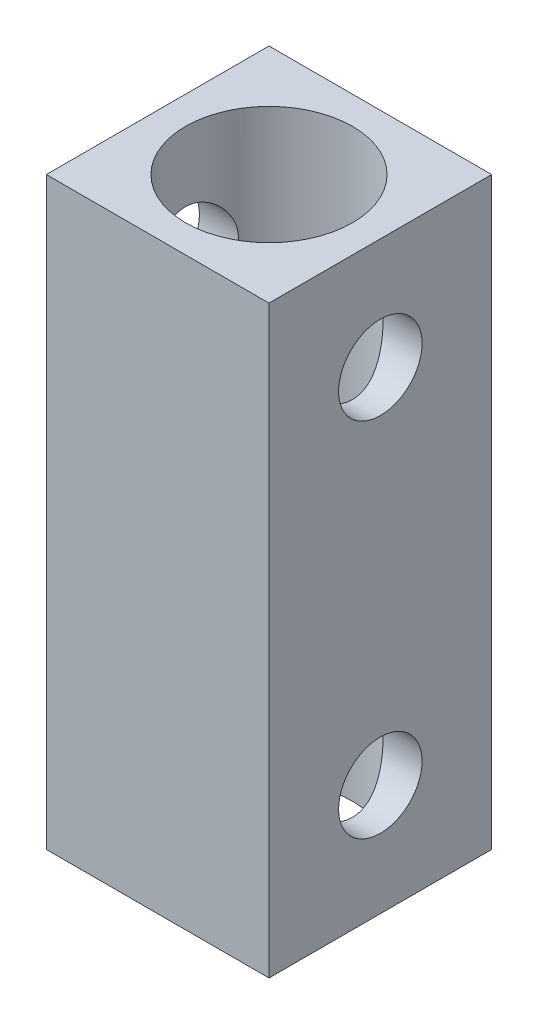
SolidWorks part; units mm, degrees
ref_plane "Front Plane" through (0, 0, 0) normal (0, 0, 1) x (1, 0, 0)
ref_plane "Top Plane" through (0, 0, 0) normal (0, 1, 0) x (1, 0, 0)
ref_plane "Right Plane" through (0, 0, 0) normal (1, 0, 0) x (0, 0, -1)
sketch "Sketch1" plane through (0, 0, 0) normal (0, 1, 0) x (1, 0, 0)
  line L1 (-4, -4) -> (4, -4)
  line L2 (-4, -4) -> (-4, 4)
  line L3 (-4, 4) -> (4, 4)
  line L4 (4, -4) -> (4, 4)
  line L5 (-4, -4) -> (4, 4) construction
  line L6 (-4, 4) -> (4, -4) construction
  circle A0 centre (0, 0) radius 3
  point P0 (0, 0)
  dimension "D1" = 6
  dimension "D2" = 4
extrude "Boss-Extrude2" add sketch "Sketch1" along normal blind 21
sketch "Sketch2" plane through (4, 0, 0) normal (1, 0, 0) x (0, 0, -1)
  line L0 (-4, 0) -> (4, 0) construction
  line L2 (-4, 21) -> (4, 21) construction
  line L3 (4, 10.5) -> (-4, 10.5) construction
  line L4 (4, 21) -> (4, 0) construction
  line L5 (-4, 21) -> (-4, 0) construction
  circle A0 centre (0, 17) radius 1.5
  circle A1 centre (0, 4) radius 1.5
  point P6 (0, 0)
  dimension "D1" = 3
  dimension "D2" = 4
extrude "Cut-Extrude1" cut sketch "Sketch2" against normal up to surface (8 mm away) up to face at (-4, 10.5, 0)
